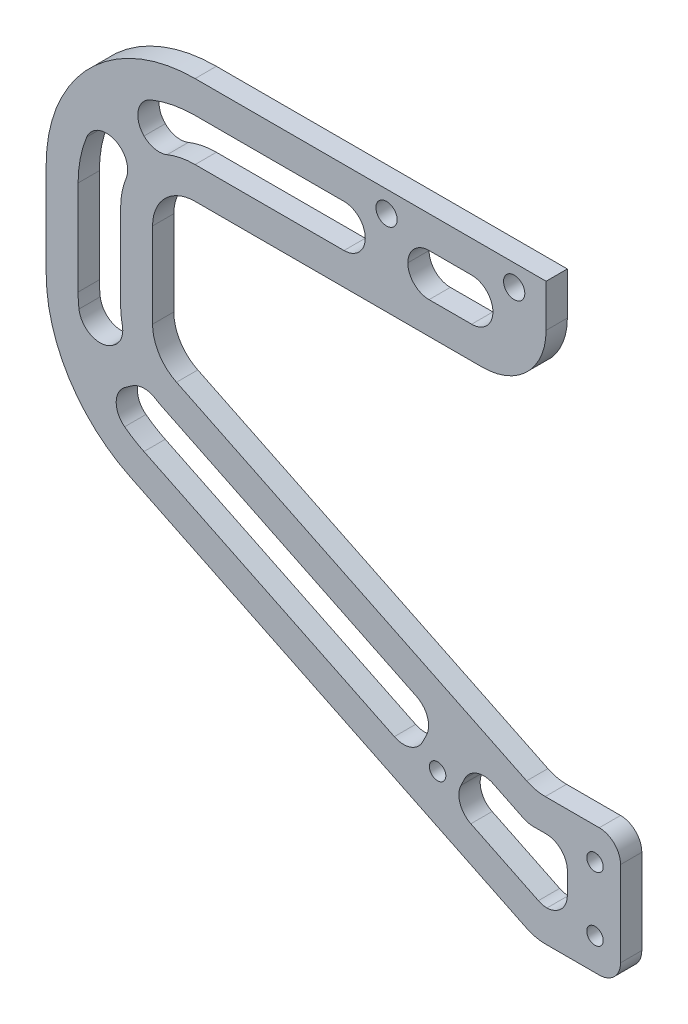
SolidWorks part; units mm, degrees
material "6061 Alloy"
ref_plane "Front Plane" through (0, 0, 0) normal (0, 0, 1) x (1, 0, 0)
ref_plane "Top Plane" through (0, 0, 0) normal (0, 1, 0) x (1, 0, 0)
ref_plane "Right Plane" through (0, 0, 0) normal (1, 0, 0) x (0, 0, -1)
sketch "Sketch1" plane through (0, 0, 0) normal (0, 0, 1) x (1, 0, 0)
  line L0 (0, 0) -> (0, 38.1)
  line L1 (0, 38.1) -> (-25.4, 38.1)
  line L2 (-139.7, 101.6) -> (-139.7, 127)
  line L3 (-127, 139.7) -> (-22.225, 139.7)
  line L4 (-22.225, 139.7) -> (-22.225, 171.45)
  line L5 (-22.225, 171.45) -> (-127, 171.45)
  line L6 (-171.45, 127) -> (-171.45, 98.8013)
  line L7 (0, 0) -> (-25.4, 0)
  line L8 (-146.4302, 58.8229) -> (-25.4, 0)
  line L9 (0, 19.05) -> (25.4, 19.05) construction
  line L10 (25.4, 19.05) -> (25.4, 120.65) construction
  line L11 (25.4, 120.65) -> (-127, 120.65) construction
  line L12 (-25.4, 38.1) -> (-132.5515, 90.1776)
  line L13 (0, 19.05) -> (-7.62, 19.05) construction
  line L14 (-7.62, 28.575) -> (-7.62, 9.525) construction
  line L15 (-7.62, 28.575) -> (-64.77, 28.575) construction
  line L16 (-69.85, 166.6875) -> (-31.75, 166.6875) construction
  line L17 (-50.8, 166.6875) -> (-50.8, 120.65) construction
  line L18 (-127, 120.65) -> (-127, 101.6) construction
  arc A0 (-171.45, 98.8013) -> (-146.4302, 58.8229) centre (-127, 98.8013) ccw
  arc A1 (-127, 171.45) -> (-171.45, 127) centre (-127, 127) ccw
  arc A2 (-139.7, 127) -> (-127, 139.7) centre (-127, 127) cw
  arc A3 (-132.5515, 90.1776) -> (-139.7, 101.6) centre (-127, 101.6) cw
  circle A7 centre (-31.75, 166.6875) radius 3.175 construction
  circle A8 centre (-69.85, 166.6875) radius 3.175 construction
  point P26 (-50.8, 166.6875)
  point P28 (-50.8, 120.65)
  dimension "D9" = 44.45
  dimension "D10" = 12.7
  dimension "D22" = 6.35
  dimension "D8" = 44.45
  dimension "D1" = 38.1
  dimension "D3" = 31.75
  dimension "D4" = 31.75
  dimension "D5" = 19.05
  dimension "D6" = 19.05
  dimension "D7" = 57.15
  dimension "D11" = 25.4
  dimension "D12" = 101.6
  dimension "D13" = 152.4
  dimension "D14" = 25.4
  dimension "D15" = 19.05
  dimension "D17" = 7.62
  dimension "D19" = 4.7625
  dimension "D20" = 38.1
  dimension "D21" = 9.525
extrude "Boss-Extrude1" add sketch "Sketch1" along normal blind 6.35
hole_wizard "1/4 (0.25) Diameter Hole1" positions "Sketch3" profile "Sketch2" hole size "1/4" standard "ANSI Inch"
sketch "Sketch3" plane through (0, 0, 6.35) normal (0, 0, 1) x (1, 0, 0)
  line L0 (-69.85, 165.1) -> (-22.225, 165.1) construction
  line L1 (-22.225, 139.7) -> (-22.225, 171.45) construction
  line L3 (-22.225, 171.45) -> (-127, 171.45) construction
  point P4 (-69.85, 165.1)
  point P6 (-31.75, 165.1)
  dimension "D1" = 9.525
  dimension "D2" = 38.1
  dimension "D3" = 6.35
sketch "Sketch2" plane through (-69.85, 165.1, 6.35) normal (1, 0, 0) x (0, -1, 0)
  line L0 (0, 0) -> (0, 11.5597)
  line L1 (0, 11.5597) -> (3.175, 9.652)
  line L2 (3.175, 9.652) -> (3.175, 0)
  line L5 (3.175, 0) -> (0, 0)
  line L10 (0, 11.5597) -> (-3.175, 9.652) construction
  line L11 (0, -6.35) -> (0, 107.95) construction
  dimension "Hole Dia." = 6.35
  dimension "Hole Depth" = 9.652
  dimension "Drill Angle" = 118
hole_wizard "#10 (0.1935) Diameter Hole1" positions "Sketch5" profile "Sketch4" hole size "#10" standard "ANSI Inch"
sketch "Sketch5" plane through (0, 0, 6.35) normal (0, 0, 1) x (1, 0, 0)
  line L0 (-7.62, 28.575) -> (-7.62, 9.525) construction
  line L2 (0, 19.05) -> (-7.62, 19.05) construction
  line L3 (0, 0) -> (0, 38.1) construction
  line L6 (-54.61, 28.575) -> (-7.62, 28.575) construction
  point P0 (-7.62, 28.575)
  point P2 (-7.62, 9.525)
  point P18 (-54.61, 28.575)
  dimension "D1" = 19.05
  dimension "D2" = 7.62
  dimension "D3" = 46.99
sketch "Sketch4" plane through (-7.62, 28.575, 6.35) normal (1, 0, 0) x (0, -1, 0)
  line L0 (0, 0) -> (0, 11.1286)
  line L1 (0, 11.1286) -> (2.4574, 9.652)
  line L2 (2.4574, 9.652) -> (2.4574, 0)
  line L5 (2.4574, 0) -> (0, 0)
  line L10 (0, 11.1286) -> (-2.4575, 9.652) construction
  line L11 (0, -6.35) -> (0, 107.95) construction
  dimension "Hole Dia." = 4.9149
  dimension "Hole Depth" = 9.652
  dimension "Drill Angle" = 118
fillet "Fillet1" radius 12.7 2 edges at (-25.4, 0, 3.175) (-25.4, 38.1, 3.175)
fillet "Fillet2" radius 6.35 2 edges at (0, 0, 3.175) (0, 38.1, 3.175)
sketch "Sketch7" plane through (0, 0, 6.35) normal (0, 0, 1) x (1, 0, 0)
  line L0 (-12.7, 28.575) -> (-22.4772, 28.575)
  line L1 (-32.1924, 30.8108) -> (-43.7363, 36.4214)
  line L2 (-50.3881, 22.7351) -> (-23.8651, 9.8444)
  line L3 (-22.4772, 9.525) -> (-12.7, 9.525)
  line L4 (-12.7, 28.575) -> (-12.7, 9.525)
  line L5 (-50.3881, 22.7351) -> (-43.7363, 36.4214)
  line L6 (-32.1924, 30.8108) -> (-136.7151, 81.6108) construction
  line L7 (-142.2666, 67.3897) -> (-23.8651, 9.8444) construction
  line L8 (-22.4772, 9.525) -> (-6.35, 9.525) construction
  line L9 (-6.35, 28.575) -> (-22.4772, 28.575) construction
  line L10 (-22.4772, 0) -> (-6.35, 0)
  line L11 (0, 6.35) -> (0, 31.75)
  line L12 (-6.35, 38.1) -> (-22.4772, 38.1)
  line L13 (-28.0287, 39.3776) -> (-132.5515, 90.1776)
  line L14 (-139.7, 101.6) -> (-139.7, 127)
  line L15 (-127, 139.7) -> (-22.225, 139.7)
  line L16 (-22.225, 139.7) -> (-22.225, 171.45)
  line L17 (-22.225, 171.45) -> (-127, 171.45)
  line L18 (-171.45, 127) -> (-171.45, 98.8013)
  line L19 (-146.4302, 58.8229) -> (-28.0287, 1.2776)
  line L20 (-161.925, 133.35) -> (-161.925, 95.25)
  line L21 (0, 6.35) -> (0, 31.75) construction
  line L22 (-161.925, 95.25) -> (-149.225, 95.25)
  line L23 (-149.225, 133.35) -> (-149.225, 95.25)
  line L24 (-139.7, 101.6) -> (-139.7, 127) construction
  line L25 (-127, 139.7) -> (-22.225, 139.7) construction
  line L26 (-22.225, 139.7) -> (-22.225, 171.45) construction
  line L27 (-22.225, 171.45) -> (-127, 171.45) construction
  line L28 (-171.45, 127) -> (-171.45, 98.8013) construction
  line L29 (-149.225, 133.35) -> (-161.925, 133.35)
  line L30 (-133.35, 158.75) -> (-133.35, 146.05)
  line L31 (-133.35, 146.05) -> (-79.375, 146.05)
  line L32 (-79.375, 146.05) -> (-79.375, 158.75)
  line L33 (-28.0287, 39.3776) -> (-132.5515, 90.1776) construction
  line L34 (-28.0287, 39.3776) -> (-132.5515, 90.1776)
  line L35 (-79.375, 158.75) -> (-133.35, 158.75)
  line L36 (-28.0287, 39.3776) -> (-132.5515, 90.1776) construction
  line L37 (-146.4302, 58.8229) -> (-28.0287, 1.2776) construction
  line L38 (-22.4772, 0) -> (-6.35, 0) construction
  line L39 (-6.35, 38.1) -> (-22.4772, 38.1) construction
  line L40 (-60.325, 158.75) -> (-60.325, 146.05)
  line L41 (-60.325, 146.05) -> (-41.275, 146.05)
  line L42 (-41.275, 146.05) -> (-41.275, 158.75)
  line L43 (-41.275, 158.75) -> (-60.325, 158.75)
  line L49 (-123.693, 75.2818) -> (-55.1586, 41.9729)
  line L50 (-55.1586, 41.9729) -> (-61.8105, 28.2865)
  line L51 (-61.8105, 28.2865) -> (-130.3448, 61.5955)
  line L52 (-130.3448, 61.5955) -> (-123.693, 75.2818)
  line L53 (-146.4302, 58.8229) -> (-28.0287, 1.2776) construction
  line L54 (-50.3881, 22.7351) -> (-61.8105, 28.2865) construction
  line L55 (-54.61, 28.575) -> (-45.2838, 47.7639) construction
  arc A0 (-32.1924, 30.8108) -> (-22.4772, 28.575) centre (-22.4772, 50.8) ccw
  arc A1 (-23.8651, 9.8444) -> (-22.4772, 9.525) centre (-22.4772, 12.7) ccw
  circle A2 centre (-69.85, 165.1) radius 3.175 construction
  circle A3 centre (-31.75, 165.1) radius 3.175 construction
  arc A8 (-6.35, 0) -> (0, 6.35) centre (-6.35, 6.35) ccw
  arc A9 (0, 31.75) -> (-6.35, 38.1) centre (-6.35, 31.75) ccw
  arc A10 (-28.0287, 39.3776) -> (-22.4772, 38.1) centre (-22.4772, 50.8) ccw
  arc A11 (-139.7, 101.6) -> (-132.5515, 90.1776) centre (-127, 101.6) ccw
  arc A12 (-127, 139.7) -> (-139.7, 127) centre (-127, 127) ccw
  arc A13 (-127, 171.45) -> (-171.45, 127) centre (-127, 127) ccw
  arc A14 (-171.45, 98.8013) -> (-146.4302, 58.8229) centre (-127, 98.8013) ccw
  arc A15 (-28.0287, 1.2776) -> (-22.4772, 0) centre (-22.4772, 12.7) ccw
  arc A16 (-6.35, 0) -> (0, 6.35) centre (-6.35, 6.35) ccw construction
  arc A17 (0, 31.75) -> (-6.35, 38.1) centre (-6.35, 31.75) ccw construction
  arc A18 (-28.0287, 39.3776) -> (-22.4772, 38.1) centre (-22.4772, 50.8) ccw construction
  arc A19 (-139.7, 101.6) -> (-132.5515, 90.1776) centre (-127, 101.6) ccw construction
  arc A20 (-127, 139.7) -> (-139.7, 127) centre (-127, 127) ccw construction
  arc A21 (-127, 171.45) -> (-171.45, 127) centre (-127, 127) ccw construction
  arc A22 (-171.45, 98.8013) -> (-146.4302, 58.8229) centre (-127, 98.8013) ccw construction
  arc A23 (-28.0287, 1.2776) -> (-22.4772, 0) centre (-22.4772, 12.7) ccw construction
  point P46 (-56.0993, 25.5108)
  point P63 (-149.225, 114.3)
  point P64 (-139.7, 114.3)
  dimension "D11" = 9.525
  dimension "D3" = 9.525
  dimension "D4" = 9.525
  dimension "D5" = 12.7
  dimension "D6" = 12.7
  dimension "D7" = 76.2
  dimension "D8" = 38.1
  dimension "D9" = 9.525
  dimension "D10" = 9.525
  dimension "D12" = 9.525
  dimension "D13" = 6.35
  dimension "D14" = 12.7
  dimension "D15" = 9.525
  dimension "D16" = 53.975
  dimension "D1" = 0
  dimension "D2" = 9.525
extrude "Cut-Extrude2" [suppressed] cut sketch "Sketch7" against normal up to next contours L52 L51 L50 L49 | L23 L29 L20 L22 | L32 L35 L30 L31 | L42 L43 L40 L41 | L5 L1 A0 L0 L4 L3 A1 L2
fillet "Fillet3" [suppressed] radius 6.35
sketch "Sketch8" plane through (0, 0, 6.35) normal (0, 0, 1) x (1, 0, 0)
  line L0 (-158.4309, 158.4309) -> (-135.9803, 135.9803) construction
  line L1 (-164.6794, 75.2203) -> (-137.4037, 94.3163) construction
  line L2 (-45.2838, 47.7639) -> (-60.2629, 16.944) construction
  line L3 (-28.0287, 39.3776) -> (-132.5515, 90.1776) construction
  line L4 (-146.4302, 58.8229) -> (-28.0287, 1.2776) construction
  line L5 (-123.6324, 130.3676) -> (-130.3676, 123.6324) construction
  line L6 (-101.6, 171.45) -> (-101.6, 161.925) construction
  line L7 (-22.225, 171.45) -> (-127, 171.45) construction
  line L8 (-101.6, 139.7) -> (-101.6, 149.225) construction
  line L9 (-127, 139.7) -> (-22.225, 139.7) construction
  line L10 (-76.2, 161.925) -> (-127, 161.925)
  line L11 (-127, 149.225) -> (-76.2, 149.225)
  line L12 (-76.2, 149.225) -> (-76.2, 161.925)
  line L13 (-148.0974, 154.8326) -> (-138.9828, 145.718)
  line L14 (-69.85, 171.45) -> (-69.85, 139.7) construction
  line L15 (-31.75, 171.45) -> (-31.75, 139.7) construction
  line L16 (-161.925, 127) -> (-161.925, 98.8013)
  line L17 (-149.225, 127) -> (-149.225, 101.6)
  line L18 (-154.8326, 148.0974) -> (-145.718, 138.9828)
  line L19 (-153.5499, 88.8258) -> (-148.0871, 81.023) construction
  line L20 (-159.0667, 84.9635) -> (-147.515, 93.0509)
  line L21 (-142.0522, 85.2482) -> (-154.1221, 76.7979)
  line L22 (-136.7151, 81.6108) -> (-55.1586, 41.9729)
  line L23 (-142.2666, 67.3897) -> (-61.8105, 28.2865)
  line L24 (-60.3212, 31.3507) -> (-48.8988, 25.7993) construction
  line L25 (-61.8105, 28.2865) -> (-55.1586, 41.9729)
  line L26 (-76.2, 155.575) -> (-63.5, 155.575) construction
  line L27 (-43.7363, 36.4214) -> (-27.5921, 28.575)
  line L28 (-27.5921, 28.575) -> (-15.875, 28.575)
  line L29 (-15.875, 28.575) -> (-15.875, 9.525)
  line L30 (-15.875, 9.525) -> (-23.2079, 9.525)
  line L31 (-23.2079, 9.525) -> (-50.3881, 22.7351)
  line L32 (-50.3881, 22.7351) -> (-43.7363, 36.4214)
  line L34 (0, 6.35) -> (0, 31.75) construction
  line L35 (-15.875, 9.525) -> (-15.875, 0) construction
  line L36 (-22.4772, 0) -> (-6.35, 0) construction
  line L37 (-15.875, 28.575) -> (-15.875, 38.1) construction
  line L38 (-6.35, 38.1) -> (-22.4772, 38.1) construction
  line L39 (-38.1, 155.575) -> (-25.4, 155.575) construction
  line L41 (-63.5, 161.925) -> (-38.1, 161.925)
  line L42 (-63.5, 161.925) -> (-63.5, 149.225)
  line L43 (-63.5, 149.225) -> (-38.1, 149.225)
  line L44 (-38.1, 161.925) -> (-38.1, 149.225)
  arc A0 (-127, 171.45) -> (-171.45, 127) centre (-127, 127) ccw construction
  arc A1 (-127, 139.7) -> (-139.7, 127) centre (-127, 127) ccw construction
  arc A2 (-171.45, 98.8013) -> (-146.4302, 58.8229) centre (-127, 98.8013) ccw construction
  arc A3 (-139.7, 101.6) -> (-132.5515, 90.1776) centre (-127, 101.6) ccw construction
  arc A4 (-127, 149.225) -> (-138.9828, 145.718) centre (-127, 127) ccw
  arc A5 (-127, 161.925) -> (-148.0974, 154.8326) centre (-127, 127) ccw
  arc A6 (-145.718, 138.9828) -> (-149.225, 127) centre (-127, 127) ccw
  arc A7 (-154.8326, 148.0974) -> (-161.925, 127) centre (-127, 127) ccw
  arc A8 (-149.225, 101.6) -> (-147.515, 93.0509) centre (-127, 101.6) ccw
  arc A9 (-161.925, 98.8013) -> (-159.0667, 84.9635) centre (-127, 98.8013) ccw
  arc A10 (-142.0522, 85.2482) -> (-136.7151, 81.6108) centre (-127, 101.6) ccw
  arc A11 (-154.1221, 76.7979) -> (-142.2666, 67.3897) centre (-127, 98.8013) ccw
  point P8 (-127, 127)
  point P9 (-127, 127)
  point P18 (-127, 101.6)
  point P19 (-150.8185, 84.9244)
  point P26 (-54.61, 28.575)
  point P47 (-69.85, 165.1)
  point P48 (-31.75, 165.1)
  point P77 (-69.85, 155.575)
  point P94 (-31.75, 155.575)
  dimension "D1" = 9.525
  dimension "D2" = 9.525
  dimension "D3" = 12.7
  dimension "D4" = 12.7
  dimension "D5" = 15.875
extrude "Cut-Extrude3" cut sketch "Sketch8" against normal through all
fillet "Fillet4" radius 6.35 22 edges at (-27.5921, 28.575, 3.175) (-23.2079, 9.525, 3.175) (-15.875, 9.525, 3.175) (-15.875, 28.575, 3.175) (-50.3881, 22.7351, 3.175) (-43.7363, 36.4214, 3.175) (-55.1586, 41.9729, 3.175) (-61.8105, 28.2865, 3.175) (-154.1221, 76.7979, 3.175) (-142.0522, 85.2482, 3.175) (-147.515, 93.0509, 3.175) (-159.0667, 84.9635, 3.175) (-154.8326, 148.0974, 3.175) (-145.718, 138.9828, 3.175) (-138.9828, 145.718, 3.175) (-148.0974, 154.8326, 3.175) (-76.2, 149.225, 3.175) (-76.2, 161.925, 3.175) (-38.1, 149.225, 3.175) (-38.1, 161.925, 3.175) (-63.5, 149.225, 3.175) (-63.5, 161.925, 3.175)
fillet "Fillet5" radius 19.05 1 edges at (-22.225, 139.7, 3.175)
